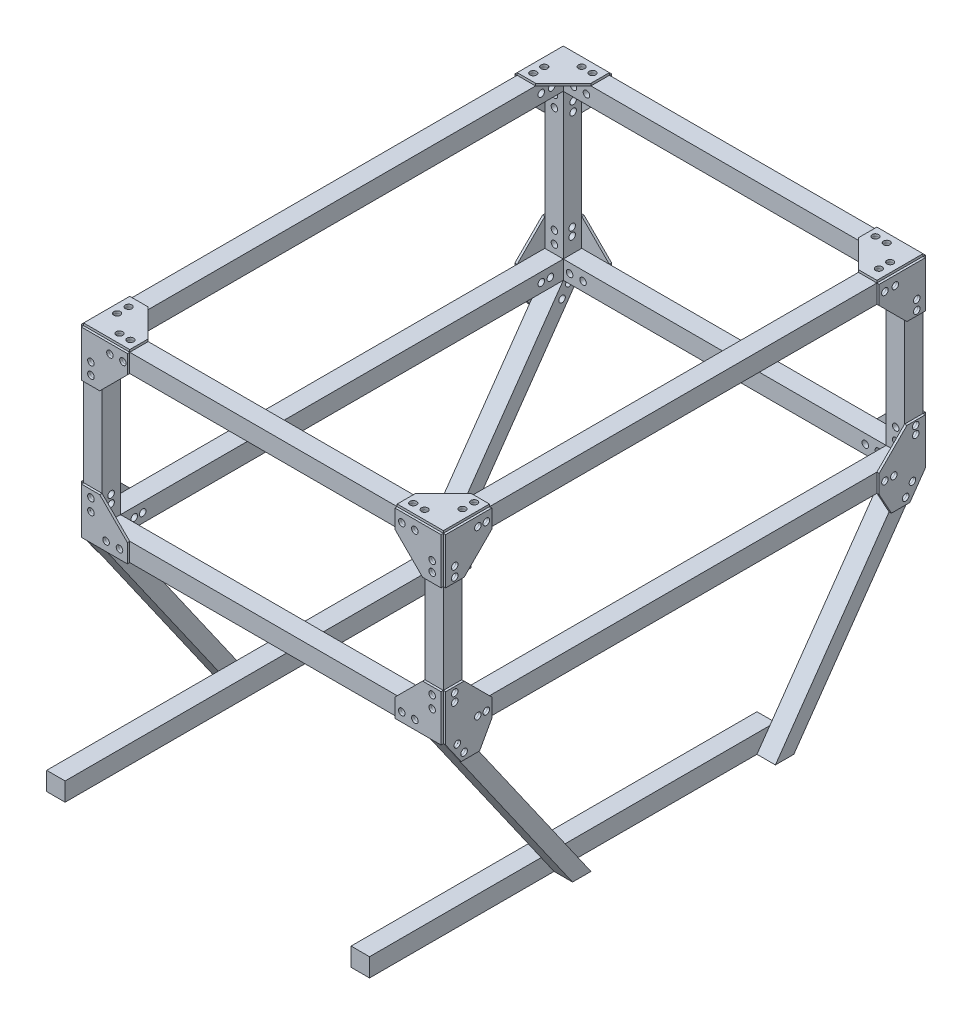
SolidWorks part; units mm, degrees
ref_plane "Front Plane" through (0, 0, 0) normal (0, 0, 1) x (1, 0, 0)
ref_plane "Top Plane" through (0, 0, 0) normal (0, 1, 0) x (1, 0, 0)
ref_plane "Right Plane" through (0, 0, 0) normal (1, 0, 0) x (0, 0, -1)
sketch "Sketch1" plane through (0, 0, 0) normal (0, 0, 1) x (1, 0, 0)
  line L1 (0, 0) -> (12.7, 0)
  line L2 (0, 0) -> (0, 12.7)
  line L3 (0, 12.7) -> (12.7, 12.7)
  line L4 (12.7, 0) -> (12.7, 12.7)
  dimension "D1" = 12.7
  dimension "D2" = 12.7
extrude "Boss-Extrude1" add sketch "Sketch1" along normal blind 304.8
sketch "Sketch3" plane through (12.7, 0, 0) normal (1, 0, 0) x (0, 0, -1)
  line L1 (0, 12.7) -> (12.7, 12.7)
  line L2 (0, 12.7) -> (0, 0)
  line L3 (0, 0) -> (12.7, 0)
  line L4 (12.7, 12.7) -> (12.7, 0)
  line L5 (-304.8, 12.7) -> (-317.5, 12.7)
  line L6 (-304.8, 12.7) -> (-304.8, 0)
  line L7 (-304.8, 0) -> (-317.5, 0)
  line L8 (-317.5, 12.7) -> (-317.5, 0)
  dimension "D1" = 12.7
  dimension "D2" = 12.7
extrude "Boss-Extrude2" add sketch "Sketch3" along normal blind 222.25 and the other way up to vertex (12.7 mm away) separate body other way up to point (0, 12.7, 0)
sketch "Sketch5" plane through (0, 0, 304.8) normal (0, 0, -1) x (-1, 0, 0)
  line L1 (-234.95, 12.7) -> (-247.65, 12.7)
  line L2 (-234.95, 12.7) -> (-234.95, 0)
  line L3 (-234.95, 0) -> (-247.65, 0)
  line L4 (-247.65, 12.7) -> (-247.65, 0)
  dimension "D1" = 12.7
extrude "Boss-Extrude3" add sketch "Sketch5" along normal blind 317.5 and the other way up to vertex (12.7 mm away) separate body other way up to point (234.95, 12.7, 317.5)
sketch "Sketch6" plane through (0, 0, 0) normal (0, -1, 0) x (1, 0, 0)
  line L0 (247.65, 317.5) -> (247.65, -12.7) construction
  line L1 (0, 317.5) -> (12.7, 317.5)
  line L2 (0, 317.5) -> (0, 304.8)
  line L3 (0, 304.8) -> (12.7, 304.8)
  line L4 (12.7, 317.5) -> (12.7, 304.8)
  line L5 (234.95, 317.5) -> (247.65, 317.5)
  line L6 (234.95, 317.5) -> (234.95, 304.8)
  line L7 (234.95, 304.8) -> (247.65, 304.8)
  line L8 (247.65, 317.5) -> (247.65, 304.8)
  line L10 (0, -12.7) -> (12.7, -12.7)
  line L11 (0, -12.7) -> (0, 0)
  line L12 (0, 0) -> (12.7, 0)
  line L13 (12.7, -12.7) -> (12.7, 0)
  line L14 (247.65, -12.7) -> (234.95, -12.7)
  line L15 (247.65, -12.7) -> (247.65, 0)
  line L16 (247.65, 0) -> (234.95, 0)
  line L17 (234.95, -12.7) -> (234.95, 0)
extrude "Boss-Extrude4" add sketch "Sketch6" along normal blind 100 separate body
sketch "Sketch8" plane through (247.65, 0, 0) normal (1, 0, 0) x (0, 0, -1)
  line L1 (-317.5, -100) -> (-304.8, -100)
  line L2 (-317.5, -100) -> (-317.5, -112.7)
  line L3 (-317.5, -112.7) -> (-304.8, -112.7)
  line L4 (-304.8, -100) -> (-304.8, -112.7)
  dimension "D1" = 12.7
  dimension "D2" = 12.7
extrude "Boss-Extrude6" add sketch "Sketch8" against normal blind 247.65 separate body
sketch "Sketch9" plane through (0, 0, 304.8) normal (0, 0, -1) x (-1, 0, 0)
  line L1 (-247.65, -112.7) -> (-234.95, -112.7)
  line L2 (-247.65, -112.7) -> (-247.65, -100)
  line L3 (-247.65, -100) -> (-234.95, -100)
  line L4 (-234.95, -112.7) -> (-234.95, -100)
  line L5 (0, -112.7) -> (-12.7, -112.7)
  line L6 (0, -112.7) -> (0, -100)
  line L7 (0, -100) -> (-12.7, -100)
  line L8 (-12.7, -112.7) -> (-12.7, -100)
extrude "Boss-Extrude8" add sketch "Sketch9" along normal blind 317.5 separate body
sketch "Sketch10" plane through (234.95, 0, 0) normal (-1, 0, 0) x (0, 0, 1)
  line L1 (-12.7, -112.7) -> (0, -112.7)
  line L2 (-12.7, -112.7) -> (-12.7, -100)
  line L3 (-12.7, -100) -> (0, -100)
  line L4 (0, -112.7) -> (0, -100)
extrude "Boss-Extrude9" add sketch "Sketch10" along normal blind 222.25 separate body
sketch "Sketch12" plane through (0, 0, 0) normal (-1, 0, 0) x (0, 0, 1)
  line L0 (-12.7, -112.7) -> (0, -112.7)
  line L1 (-12.7, -112.7) -> (304.8, -112.7) construction
  line L2 (0, -112.7) -> (88.9264, -239.7)
  line L3 (88.9264, -239.7) -> (76.2264, -239.7)
  line L4 (76.2264, -239.7) -> (-12.7, -112.7)
  dimension "D1" = 127
  dimension "D2" = 12.7
  dimension "D3" = 12.7
  dimension "D4" = 55
extrude "Boss-Extrude11" add sketch "Sketch12" against normal blind 12.7 separate body
sketch "Sketch13" plane through (0, 0, 0) normal (-1, 0, 0) x (0, 0, 1)
  line L0 (317.5, -112.7) -> (304.8, -112.7)
  line L1 (304.8, -112.7) -> (215.8736, -239.7)
  line L2 (215.8736, -239.7) -> (228.5736, -239.7)
  line L3 (228.5736, -239.7) -> (317.5, -112.7)
  dimension "D1" = 127
  dimension "D2" = 12.7
  dimension "D3" = 55
extrude "Boss-Extrude12" add sketch "Sketch13" against normal blind 12.7 separate body
sketch "Sketch14" plane through (247.65, 0, 0) normal (1, 0, 0) x (0, 0, -1)
  line L0 (-317.5, -112.7) -> (-228.5736, -239.7)
  line L1 (-228.5736, -239.7) -> (-215.8736, -239.7)
  line L2 (-215.8736, -239.7) -> (-304.8, -112.7)
  line L3 (-304.8, -112.7) -> (-317.5, -112.7)
  line L4 (-88.9264, -239.7) -> (-76.2264, -239.7)
  line L5 (-76.2264, -239.7) -> (12.7, -112.7)
  line L6 (12.7, -112.7) -> (0, -112.7)
  line L7 (0, -112.7) -> (-88.9264, -239.7)
extrude "Boss-Extrude13" add sketch "Sketch14" against normal blind 12.7 separate body
sketch "Sketch15" plane through (12.7, 0, 0) normal (1, 0, 0) x (0, 0, -1)
  line L0 (-76.2264, -239.7) -> (-76.2264, -227)
  line L1 (-76.2264, -227) -> (-355.6264, -227)
  line L2 (-355.6264, -227) -> (-355.6264, -239.7)
  line L3 (-355.6264, -239.7) -> (-76.2264, -239.7)
  dimension "D1" = 12.7
  dimension "D2" = 279.4
extrude "Boss-Extrude15" add sketch "Sketch15" along normal blind 12.7 separate body
sketch "Sketch16" plane through (234.95, 0, 0) normal (-1, 0, 0) x (0, 0, 1)
  line L0 (76.2264, -239.7) -> (76.2264, -227)
  line L1 (76.2264, -227) -> (355.6264, -227)
  line L2 (355.6264, -227) -> (355.6264, -239.7)
  line L3 (355.6264, -239.7) -> (76.2264, -239.7)
  dimension "D1" = 12.7
  dimension "D2" = 279.4
extrude "Boss-Extrude16" add sketch "Sketch16" along normal blind 12.7 separate body
sketch "Sketch17" plane through (0, 0, 0) normal (-1, 0, 0) x (0, 0, 1)
  line L0 (-12.7, 12.7) -> (19.05, 12.7)
  line L1 (304.8, 12.7) -> (0, 12.7) construction
  line L2 (19.05, 12.7) -> (19.05, 0)
  line L3 (304.8, 0) -> (0, 0) construction
  line L4 (19.05, 0) -> (0, -19.05)
  line L5 (0, -100) -> (0, 0) construction
  line L6 (0, -19.05) -> (-12.7, -19.05)
  line L7 (-12.7, -100) -> (-12.7, 0) construction
  line L8 (-12.7, -19.05) -> (-12.7, 12.7)
  line L9 (317.5, 12.7) -> (285.75, 12.7)
  line L10 (285.75, 12.7) -> (285.75, 0)
  line L11 (285.75, 0) -> (304.8, -19.05)
  line L12 (304.8, -100) -> (304.8, 0) construction
  line L13 (304.8, -19.05) -> (317.5, -19.05)
  line L14 (317.5, -100) -> (317.5, 0) construction
  line L15 (317.5, -19.05) -> (317.5, 12.7)
  line L16 (-12.7, -112.7) -> (-12.7, -80.95)
  line L17 (-12.7, -80.95) -> (0, -80.95)
  line L18 (0, -80.95) -> (19.05, -100)
  line L19 (-12.7, -100) -> (304.8, -100) construction
  line L20 (19.05, -100) -> (19.05, -112.7)
  line L21 (-12.7, -112.7) -> (304.8, -112.7) construction
  line L23 (317.5, -112.7) -> (317.5, -80.95)
  line L24 (317.5, -80.95) -> (304.8, -80.95)
  line L25 (304.8, -80.95) -> (285.75, -100)
  line L26 (285.75, -100) -> (285.75, -112.7)
  line L28 (-12.7, -112.7) -> (-2.0288, -127.94)
  line L29 (-12.7, -112.7) -> (76.2264, -239.7) construction
  line L30 (-2.0288, -127.94) -> (10.6712, -127.94)
  line L31 (88.9264, -239.7) -> (0, -112.7) construction
  line L34 (317.5, -112.7) -> (306.8288, -127.94)
  line L35 (228.5736, -239.7) -> (317.5, -112.7) construction
  line L36 (306.8288, -127.94) -> (294.1288, -127.94)
  line L37 (304.8, -112.7) -> (215.8736, -239.7) construction
  line L40 (19.05, -112.7) -> (10.6712, -127.94)
  line L41 (285.75, -112.7) -> (294.1288, -127.94)
  circle A0 centre (-6.7847, -15.7208) radius 2.25
  circle A1 centre (-6.7847, -9.1845) radius 2.25
  circle A2 centre (15.1208, 6.3614) radius 2.25
  circle A3 centre (7.9661, 6.3614) radius 2.25
  circle A4 centre (-3.8386, -116.1836) radius 2.25
  circle A5 centre (0.8299, -123.4038) radius 2.25
  circle A6 centre (-6.1056, -84.0258) radius 2.25
  circle A7 centre (-6.1056, -89.426) radius 2.25
  circle A8 centre (15.1208, -106.4791) radius 2.25
  circle A9 centre (8.9324, -106.4791) radius 2.25
  circle A10 centre (289.5093, 6.3614) radius 2.25
  circle A11 centre (295.3157, 6.3614) radius 2.25
  circle A12 centre (311.2568, -15.7208) radius 2.25
  circle A13 centre (311.2568, -9.1845) radius 2.25
  circle A14 centre (311.2568, -84.6779) radius 2.25
  circle A16 centre (289.5093, -106.4791) radius 2.25
  circle A17 centre (295.3157, -106.4791) radius 2.25
  circle A18 centre (309.4689, -116.1836) radius 2.25
  circle A19 centre (304.8, -123.4038) radius 2.25
  circle A20 centre (311.2568, -90.3243) radius 2.25
  dimension "D7" = 4.5
  dimension "D8" = 4.5
  dimension "D9" = 4.5
  dimension "D10" = 4.5
  dimension "D11" = 4.5
  dimension "D12" = 4.5
  dimension "D13" = 4.5
  dimension "D14" = 4.5
  dimension "D15" = 4.5
  dimension "D16" = 4.5
  dimension "D17" = 4.5
  dimension "D18" = 4.5
  dimension "D19" = 4.5
  dimension "D1" = 31.75
  dimension "D2" = 31.75
  dimension "D3" = 31.75
  dimension "D4" = 31.75
  dimension "D5" = 15.24
  dimension "D6" = 15.24
extrude "Boss-Extrude17" add sketch "Sketch17" along normal blind 1.5875 separate body
sketch "Sketch18" plane through (0, 0, 317.5) normal (0, 0, 1) x (1, 0, 0)
  line L0 (0, 12.7) -> (31.75, 12.7)
  line L1 (0, 12.7) -> (234.95, 12.7) construction
  line L2 (31.75, 12.7) -> (31.75, 0)
  line L3 (0, 0) -> (234.95, 0) construction
  line L4 (31.75, 0) -> (12.7, -19.05)
  line L5 (12.7, -100) -> (12.7, 0) construction
  line L6 (12.7, -19.05) -> (0, -19.05)
  line L7 (0, -100) -> (0, 0) construction
  line L8 (0, -19.05) -> (0, 12.7)
  line L9 (247.65, 12.7) -> (247.65, -19.05)
  line L10 (247.65, -100) -> (247.65, 0) construction
  line L11 (247.65, -19.05) -> (234.95, -19.05)
  line L12 (234.95, -100) -> (234.95, 0) construction
  line L13 (234.95, -19.05) -> (215.9, 0)
  line L14 (215.9, 0) -> (215.9, 12.7)
  line L15 (215.9, 12.7) -> (247.65, 12.7)
  line L16 (0, -112.7) -> (31.75, -112.7)
  line L17 (0, -112.7) -> (247.65, -112.7) construction
  line L18 (31.75, -112.7) -> (31.75, -100)
  line L19 (0, -100) -> (247.65, -100) construction
  line L20 (31.75, -100) -> (12.7, -80.95)
  line L21 (12.7, -80.95) -> (0, -80.95)
  line L22 (0, -80.95) -> (0, -112.7)
  line L23 (247.65, -112.7) -> (247.65, -80.95)
  line L24 (247.65, -80.95) -> (234.95, -80.95)
  line L25 (234.95, -80.95) -> (215.9, -100)
  line L26 (215.9, -100) -> (215.9, -112.7)
  line L27 (215.9, -112.7) -> (247.65, -112.7)
  dimension "D1" = 31.75
  dimension "D2" = 31.75
  dimension "D3" = 31.75
  dimension "D4" = 31.75
  dimension "D5" = 31.75
  dimension "D6" = 31.75
  dimension "D7" = 31.75
extrude "Boss-Extrude18" add sketch "Sketch18" along normal blind 1.5875 separate body
sketch "Sketch19" plane through (247.65, 0, 0) normal (1, 0, 0) x (0, 0, -1)
  line L0 (-317.5, 12.7) -> (-285.75, 12.7)
  line L1 (-317.5, 12.7) -> (12.7, 12.7) construction
  line L2 (-285.75, 12.7) -> (-285.75, 0)
  line L3 (-317.5, 0) -> (12.7, 0) construction
  line L4 (-285.75, 0) -> (-304.8, -19.05)
  line L5 (-304.8, -100) -> (-304.8, 0) construction
  line L6 (-304.8, -19.05) -> (-317.5, -19.05)
  line L7 (-317.5, -100) -> (-317.5, 0) construction
  line L8 (-317.5, -19.05) -> (-317.5, 12.7)
  line L9 (12.7, 12.7) -> (12.7, -19.05)
  line L10 (12.7, -19.05) -> (0, -19.05)
  line L11 (0, -100) -> (0, 0) construction
  line L12 (0, -19.05) -> (-19.05, 0)
  line L13 (-19.05, 0) -> (-19.05, 12.7)
  line L14 (-19.05, 12.7) -> (12.7, 12.7)
  line L16 (12.7, -112.7) -> (-304.8, -112.7) construction
  line L17 (-285.75, -112.7) -> (-285.75, -100)
  line L18 (12.7, -100) -> (-304.8, -100) construction
  line L19 (-285.75, -100) -> (-304.8, -80.95)
  line L20 (-304.8, -80.95) -> (-317.5, -80.95)
  line L21 (-317.5, -80.95) -> (-317.5, -112.7)
  line L22 (12.7, -112.7) -> (12.7, -80.95)
  line L23 (12.7, -100) -> (12.7, 0) construction
  line L24 (12.7, -80.95) -> (0, -80.95)
  line L25 (0, -80.95) -> (-19.05, -100)
  line L26 (-19.05, -100) -> (-19.05, -112.7)
  line L28 (-317.5, -112.7) -> (-306.8288, -127.94)
  line L29 (-317.5, -112.7) -> (-228.5736, -239.7) construction
  line L30 (-306.8288, -127.94) -> (-294.1288, -127.94)
  line L31 (-215.8736, -239.7) -> (-304.8, -112.7) construction
  line L34 (12.7, -112.7) -> (2.0288, -127.94)
  line L35 (-76.2264, -239.7) -> (12.7, -112.7) construction
  line L36 (2.0288, -127.94) -> (-10.6712, -127.94)
  line L37 (0, -112.7) -> (-88.9264, -239.7) construction
  line L40 (-285.75, -112.7) -> (-294.1288, -127.94)
  line L41 (-19.05, -112.7) -> (-10.6712, -127.94)
  dimension "D1" = 31.75
  dimension "D2" = 31.75
  dimension "D3" = 15.24
  dimension "D4" = 15.24
extrude "Boss-Extrude19" add sketch "Sketch19" along normal blind 1.5875 separate body
sketch "Sketch20" plane through (0, 0, -12.7) normal (0, 0, -1) x (-1, 0, 0)
  line L0 (-247.65, 12.7) -> (-215.9, 12.7)
  line L1 (0, 12.7) -> (-234.95, 12.7) construction
  line L2 (-215.9, 12.7) -> (-215.9, 0)
  line L3 (0, 0) -> (-234.95, 0) construction
  line L4 (-215.9, 0) -> (-234.95, -20.3448)
  line L5 (-234.95, -100) -> (-234.95, 0) construction
  line L6 (-234.95, -20.3448) -> (-247.65, -19.05)
  line L7 (-247.65, -100) -> (-247.65, 0) construction
  line L8 (-247.65, -19.05) -> (-247.65, 12.7) construction
  line L9 (-247.65, -19.05) -> (-247.65, 12.7)
  line L10 (0, 12.7) -> (-31.75, 12.7)
  line L11 (-31.75, 12.7) -> (-31.75, 0)
  line L13 (-31.75, 0) -> (-12.7, -19.05)
  line L14 (-12.7, -19.05) -> (0, -19.05)
  line L15 (-247.65, -112.7) -> (-215.9, -112.7)
  line L16 (-12.7, -112.7) -> (-234.95, -112.7) construction
  line L17 (-215.9, -112.7) -> (-215.9, -100)
  line L18 (-12.7, -100) -> (-234.95, -100) construction
  line L19 (-215.9, -100) -> (-234.95, -80.95)
  line L20 (-234.95, -80.95) -> (-247.65, -80.95)
  line L21 (-247.65, -80.95) -> (-247.65, -112.7)
  line L22 (0, -112.7) -> (0, -80.95)
  line L23 (0, -80.95) -> (-12.7, -80.95)
  line L24 (-12.7, -100) -> (-12.7, 0) construction
  line L25 (-12.7, -80.95) -> (-31.75, -100)
  line L26 (-31.75, -100) -> (-31.75, -112.7)
  line L27 (-31.75, -112.7) -> (0, -112.7)
  line L28 (0, -19.05) -> (0, 12.7)
  circle A0 centre (-220.6293, 6.3497) radius 2.25
  circle A1 centre (-229.6227, 6.3497) radius 2.25
  circle A2 centre (-241.5436, -12.822) radius 2.25
  circle A3 centre (-241.5436, -5.7894) radius 2.25
  circle A4 centre (-241.5436, -85.8523) radius 2.25
  circle A5 centre (-241.5436, -94.1692) radius 2.25
  circle A6 centre (-229.6227, -106.4874) radius 2.25
  circle A7 centre (-220.6293, -106.4874) radius 2.25
  circle A8 centre (-28.6709, 6.3497) radius 2.25
  circle A9 centre (-19.6968, 6.3497) radius 2.25
  circle A10 centre (-6.6214, -4.8902) radius 2.25
  circle A11 centre (-6.6214, -12.822) radius 2.25
  circle A12 centre (-6.6214, -85.8523) radius 2.25
  circle A13 centre (-6.6214, -94.1692) radius 2.25
  circle A14 centre (-26.2877, -106.4874) radius 2.25
  circle A15 centre (-17.0622, -106.4874) radius 2.25
  dimension "D3" = 4.5
  dimension "D1" = 31.75
  dimension "D2" = 31.75
extrude "Boss-Extrude20" add sketch "Sketch20" along normal blind 1.5875 separate body
extrude "Cut-Extrude1" cut sketch "Sketch17<4>" against normal through all contours A2 | A3 | A1 | A0 region at (0, -15.7208, -6.7847) region at (0, -9.1845, -6.7847) region at (0, 6.3614, 15.1208) region at (0, 6.3614, 7.9661)
sketch "Sketch17<4>" plane through (0, 0, 0) normal (-1, 0, 0) x (0, 0, 1) same geometry as "Sketch17"
extrude "Cut-Extrude4" cut sketch "Sketch17<6>" against normal through all contours A6 | A7 | A9 | A8 | A4 | A5 region at (0, -116.1836, -3.8386) region at (0, -123.4038, 0.8299) region at (0, -84.0258, -6.1056) region at (0, -89.426, -6.1056) region at (0, -106.4791, 15.1208) region at (0, -106.4791, 8.9324)
sketch "Sketch17<6>" plane through (0, 0, 0) normal (-1, 0, 0) x (0, 0, 1) same geometry as "Sketch17"
extrude "Cut-Extrude5" cut sketch "Sketch17<7>" against normal through all contours A10 | A11 | A13 | A12 | A14 | A20 | A17 | A16 | A18 | A19 region at (0, 6.3614, 289.5093) region at (0, 6.3614, 295.3157) region at (0, -15.7208, 311.2568) region at (0, -9.1845, 311.2568) region at (0, -84.6779, 311.2568) region at (0, -106.4791, 289.5093) region at (0, -106.4791, 295.3157) region at (0, -116.1836, 309.4689) region at (0, -123.4038, 304.8) region at (0, -90.3243, 311.2568)
sketch "Sketch17<7>" plane through (0, 0, 0) normal (-1, 0, 0) x (0, 0, 1) same geometry as "Sketch17"
extrude "Cut-Extrude6" cut sketch "Sketch20<2>" against normal through all contours A1 | A0 | A3 | A2 | A4 | A5 | A6 | A7 | A8 | A9 | A10 | A11 | A12 | A13 | A15 | A14 region at (220.6293, 6.3497, -12.7) region at (229.6227, 6.3497, -12.7) region at (241.5436, -12.822, -12.7) region at (241.5436, -5.7894, -12.7) region at (241.5436, -85.8523, -12.7) region at (241.5436, -94.1692, -12.7) region at (229.6227, -106.4874, -12.7) region at (220.6293, -106.4874, -12.7) region at (28.6709, 6.3497, -12.7) region at (19.6968, 6.3497, -12.7) region at (6.6214, -4.8902, -12.7) region at (6.6214, -12.822, -12.7) region at (6.6214, -85.8523, -12.7) region at (6.6214, -94.1692, -12.7) region at (26.2877, -106.4874, -12.7) region at (17.0622, -106.4874, -12.7)
sketch "Sketch20<2>" plane through (0, 0, -12.7) normal (0, 0, -1) x (-1, 0, 0) same geometry as "Sketch20"
sketch "Sketch23" plane through (0, 12.7, 0) normal (0, 1, 0) x (1, 0, 0)
  line L0 (0, 12.7) -> (31.75, 12.7)
  line L1 (31.75, 12.7) -> (31.75, 0)
  line L2 (0, 0) -> (234.95, 0) construction
  line L3 (31.75, 0) -> (12.7, -19.05)
  line L4 (12.7, -304.8) -> (12.7, 0) construction
  line L5 (12.7, -19.05) -> (0, -19.05)
  line L6 (0, -19.05) -> (0, -10.6712) construction
  line L7 (0, -19.05) -> (0, 12.7)
  line L8 (247.65, 12.7) -> (215.9, 12.7)
  line L9 (215.9, 12.7) -> (215.9, 0)
  line L10 (215.9, 0) -> (234.95, -19.05)
  line L11 (234.95, -317.5) -> (234.95, 12.7) construction
  line L12 (234.95, -19.05) -> (247.65, -19.05)
  line L13 (247.65, -19.05) -> (247.65, 12.7)
  line L14 (0, -317.5) -> (0, -285.75)
  line L15 (0, -285.75) -> (0, -294.1288) construction
  line L16 (0, -304.8) -> (0, -285.75) construction
  line L17 (0, -285.75) -> (12.7, -285.75)
  line L18 (12.7, -285.75) -> (31.75, -304.8)
  line L19 (0, -304.8) -> (234.95, -304.8) construction
  line L20 (31.75, -304.8) -> (31.75, -317.5)
  line L21 (31.75, -317.5) -> (0, -317.5)
  line L22 (247.65, -317.5) -> (247.65, -285.75)
  line L23 (247.65, -285.75) -> (234.95, -285.75)
  line L24 (234.95, -355.6264) -> (234.95, -76.2264) construction
  line L25 (234.95, -285.75) -> (215.9, -304.8)
  line L26 (215.9, -304.8) -> (215.9, -317.5)
  line L27 (215.9, -317.5) -> (247.65, -317.5)
  circle A0 centre (5.8788, -6.2754) radius 2.25
  circle A1 centre (5.8788, -13.8211) radius 2.25
  circle A2 centre (18.6818, 6.6513) radius 2.25
  circle A3 centre (26.2275, 6.6513) radius 2.25
  circle A4 centre (220.941, 6.6513) radius 2.25
  circle A5 centre (228.7218, 6.6513) radius 2.25
  circle A6 centre (241.3539, -3.6455) radius 2.25
  circle A7 centre (241.3539, -11.3963) radius 2.25
  circle A8 centre (241.3539, -289.9923) radius 2.25
  circle A9 centre (241.3539, -298.0273) radius 2.25
  circle A10 centre (228.7218, -311.5067) radius 2.25
  circle A11 centre (220.941, -311.5067) radius 2.25
  circle A12 centre (5.8788, -292.3861) radius 2.25
  circle A13 centre (5.8788, -300.2922) radius 2.25
  circle A14 centre (18.6818, -311.5067) radius 2.25
  circle A15 centre (26.2275, -311.5067) radius 2.25
  dimension "D1" = 4.5
extrude "Boss-Extrude22" add sketch "Sketch23" along normal blind 1.5875 separate body
extrude "Cut-Extrude7" cut sketch "Sketch23<3>" against normal up to surface (12.7 mm away) contours A2 | A3 | A1 | A4 | A5 | A6 | A7 | A0 region at (5.8788, 12.7, 13.8211) region at (18.6818, 12.7, -6.6513) region at (26.2275, 12.7, -6.6513) region at (220.941, 12.7, -6.6513) region at (228.7218, 12.7, -6.6513) region at (241.3539, 12.7, 3.6455) region at (241.3539, 12.7, 11.3963) up to face at (117.475, 0, -6.35)
sketch "Sketch23<3>" plane through (0, 12.7, 0) normal (0, 1, 0) x (1, 0, 0) same geometry as "Sketch23"
extrude "Cut-Extrude8" cut sketch "Sketch23<4>" against normal up to surface (12.7 mm away) contours A12 | A13 | A14 | A15 | A8 | A9 | A10 | A11 region at (241.3539, 12.7, 289.9923) region at (241.3539, 12.7, 298.0273) region at (228.7218, 12.7, 311.5067) region at (220.941, 12.7, 311.5067) region at (5.8788, 12.7, 292.3861) region at (5.8788, 12.7, 300.2922) region at (18.6818, 12.7, 311.5067) region at (26.2275, 12.7, 311.5067) up to face at (117.475, 0, 311.15)
sketch "Sketch23<4>" plane through (0, 12.7, 0) normal (0, 1, 0) x (1, 0, 0) same geometry as "Sketch23"
